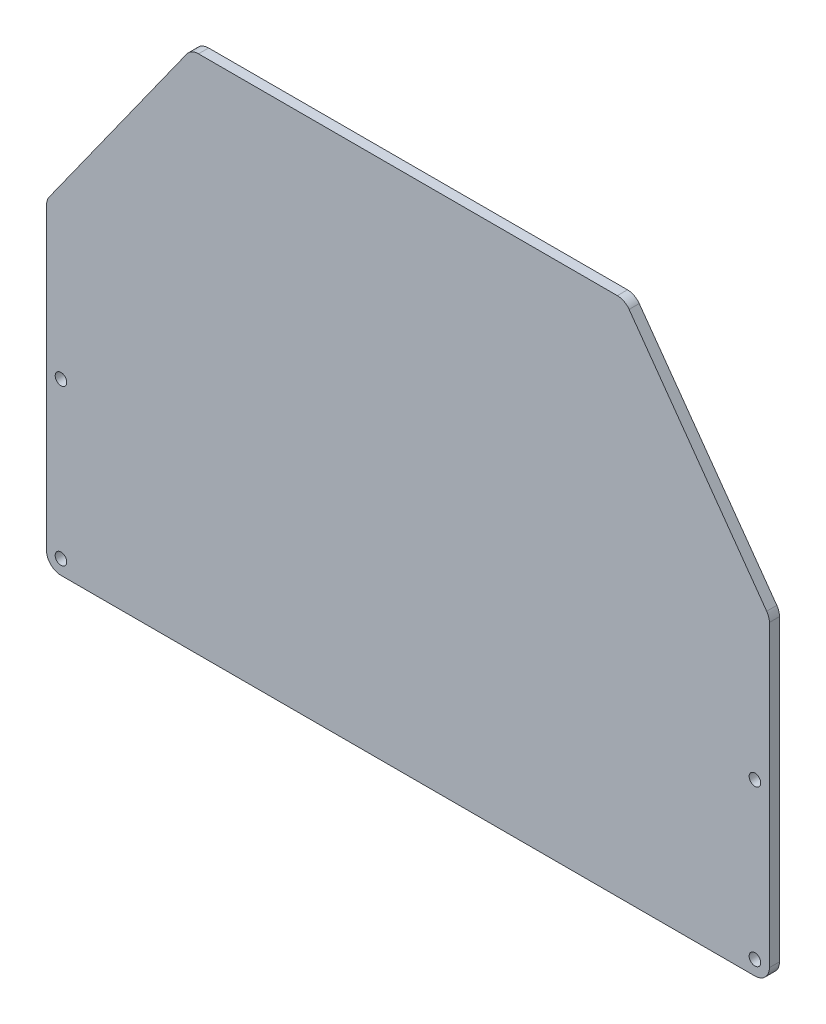
SolidWorks part; units mm, degrees
ref_plane "Plan de face" through (0, 0, 0) normal (0, 0, 1) x (1, 0, 0)
ref_plane "Plan de dessus" through (0, 0, 0) normal (0, 1, 0) x (1, 0, 0)
ref_plane "Plan de droite" through (0, 0, 0) normal (1, 0, 0) x (0, 0, -1)
sketch "Esquisse1" plane through (0, 0, 0) normal (0, 0, 1) x (1, 0, 0)
  line L1 (5, 0) -> (245, 0)
  line L2 (0, 5) -> (0, 305)
  line L3 (0, 305) -> (250, 305)
  line L4 (250, 5) -> (250, 305)
  arc A0 (250, 5) -> (245, 0) centre (245, 5) cw
  arc A1 (5, 0) -> (0, 5) centre (5, 5) cw
  point P7 (250, 0)
  point P10 (0, 0)
  dimension "D2" = 5
  dimension "D3" = 5
  dimension "D1" = 250
  dimension "D4" = 300
extrude "Boss.-Extru.1" add sketch "Esquisse1" along normal blind 3.5
sketch "Esquisse2" plane through (0, 0, 3.5) normal (0, 0, 1) x (1, 0, 0)
  line L0 (-19.0099, 5) -> (402.2953, 5) construction
  line L1 (5, 0) -> (245, 0) construction
  line L2 (5, -25.1291) -> (5, 139.966) construction
  line L3 (0, 305) -> (0, 5) construction
  line L4 (245, -22.1166) -> (245, 94.5536) construction
  line L5 (250, 5) -> (250, 305) construction
  line L6 (-9.3926, 58.8) -> (267.0784, 58.8) construction
  circle A0 centre (5, 5) radius 2
  circle A1 centre (245, 5) radius 2
  circle A2 centre (5, 58.8) radius 2
  circle A3 centre (245, 58.8) radius 2
  dimension "D1" = 4
  dimension "D2" = 4
  dimension "D7" = 4
  dimension "D8" = 4
  dimension "D3" = 5
  dimension "D4" = 5
  dimension "D5" = 5
  dimension "D6" = 53.8
extrude "Enlèv. mat.-Extru.1" cut sketch "Esquisse2" against normal through all
sketch "Esquisse3" plane through (0, 0, 3.5) normal (0, 0, 1) x (1, 0, 0)
  line L0 (0, 110) -> (50, 180)
  line L1 (50, 180) -> (200, 180)
  line L2 (200, 180) -> (250, 110)
  line L3 (125, 632.4465) -> (125, -22.4465) construction
  line L4 (250, 305) -> (0, 305) construction
  line L5 (0, 305) -> (0, 5) construction
  line L6 (250, 5) -> (250, 305) construction
  line L7 (5, 0) -> (245, 0) construction
  point P8 (125, 305)
  point P9 (125, 180)
  dimension "D1" = 110
  dimension "D2" = 110
  dimension "D3" = 150
  dimension "D4" = 180
  dimension "D5" = 180
extrude "Enlèv. mat.-Extru.2" cut sketch "Esquisse3" against normal through all and the other way through all
fillet "Congé1" radius 5 4 edges at (250, 110, 1.75) (200, 180, 1.75) (50, 180, 1.75) (0, 110, 1.75)
